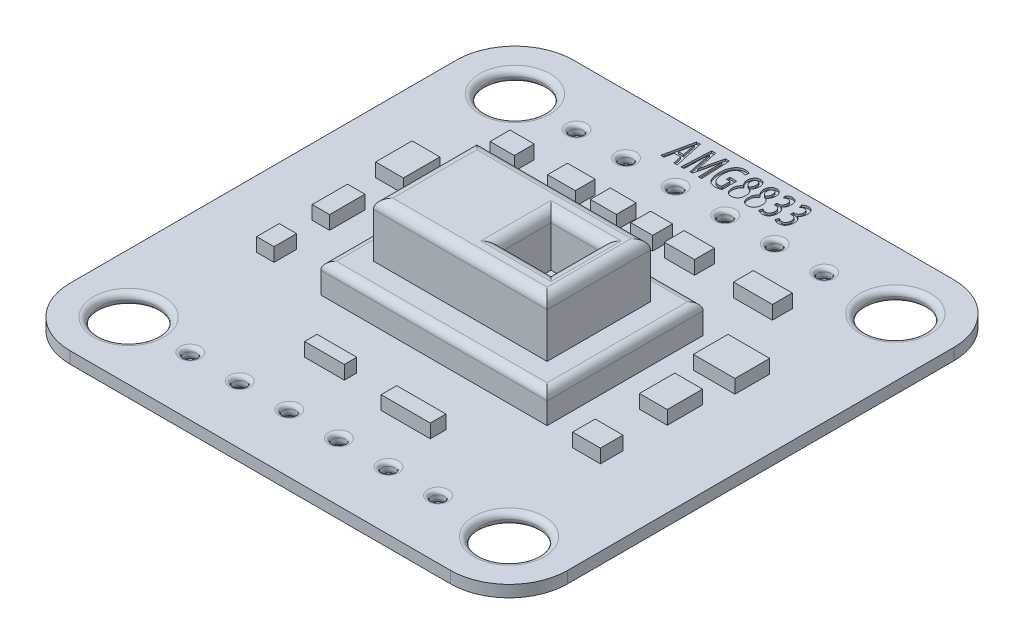
SolidWorks part; units mm, degrees
ref_plane "Alzado" through (0, 0, 0) normal (0, 0, 1) x (1, 0, 0)
ref_plane "Planta" through (0, 0, 0) normal (0, 1, 0) x (1, 0, 0)
ref_plane "Vista lateral" through (0, 0, 0) normal (1, 0, 0) x (0, 0, -1)
sketch "Croquis1" plane through (0, 0, 0) normal (0, 1, 0) x (1, 0, 0)
  line L1 (-12.75, 12.9) -> (12.75, 12.9)
  line L2 (-12.75, 12.9) -> (-12.75, -12.9)
  line L3 (-12.75, -12.9) -> (12.75, -12.9)
  line L4 (12.75, 12.9) -> (12.75, -12.9)
  line L5 (-12.75, 12.9) -> (12.75, -12.9) construction
  line L6 (-12.75, -12.9) -> (12.75, 12.9) construction
  point P0 (0, 0)
  dimension "D1" = 25.5
  dimension "D2" = 25.8
extrude "Saliente-Extruir1" add sketch "Croquis1" along normal blind 0.6
fillet "Redondeo1" radius 3 4 edges at (12.75, 0.3, 12.9) (-12.75, 0.3, 12.9) (12.75, 0.3, -12.9) (-12.75, 0.3, -12.9)
sketch "Croquis2" plane through (0, 0, 0) normal (0, -1, 0) x (1, 0, 0)
  circle A0 centre (9.75, -9.9) radius 1.5
  circle A1 centre (-9.75, -9.9) radius 1.5
  circle A2 centre (-9.75, 9.9) radius 1.5
  circle A3 centre (9.75, 9.9) radius 1.5
  dimension "D1" = 3
extrude "Cortar-Extruir1" cut sketch "Croquis2" against normal through all
fillet "Redondeo3" radius 0.3 8 edges at (-9.75, 0, 8.4) (-9.75, 0.6, 8.4) (9.75, 0, 8.4) (9.75, 0.6, 8.4) (-9.75, 0, -11.4) (-9.75, 0.6, -11.4) (9.75, 0, -11.4) (9.75, 0.6, -11.4)
sketch "Croquis3" plane through (0, 0.6, 0) normal (0, 1, 0) x (1, 0, 0)
  line L1 (-5.8, 4) -> (5.8, 4)
  line L2 (-5.8, 4) -> (-5.8, -4)
  line L3 (-5.8, -4) -> (5.8, -4)
  line L4 (5.8, 4) -> (5.8, -4)
  line L5 (-5.8, 4) -> (5.8, -4) construction
  line L6 (-5.8, -4) -> (5.8, 4) construction
  point P0 (0, 0)
  dimension "D1" = 11.6
  dimension "D2" = 8
extrude "Saliente-Extruir2" add sketch "Croquis3" along normal blind 1.5
sketch "Croquis4" plane through (0, 2.1, 0) normal (0, 1, 0) x (1, 0, 0)
  line L1 (-4.45, 2.65) -> (4.45, 2.65)
  line L2 (-4.45, 2.65) -> (-4.45, -2.65)
  line L3 (-4.45, -2.65) -> (4.45, -2.65)
  line L4 (4.45, 2.65) -> (4.45, -2.65)
  line L5 (-4.45, 2.65) -> (4.45, -2.65) construction
  line L6 (-4.45, -2.65) -> (4.45, 2.65) construction
  point P0 (0, 0)
  dimension "D1" = 5.3
  dimension "D2" = 8.9
extrude "Saliente-Extruir3" add sketch "Croquis4" along normal blind 2.8
fillet "Redondeo4" radius 0.4 4 edges at (0, 2.1, -4) (5.8, 2.1, 0) (0, 2.1, 4) (-5.8, 2.1, 0)
fillet "Redondeo5" radius 0.5 4 edges at (0, 4.9, 2.65) (-4.45, 4.9, 0) (0, 4.9, -2.65) (4.45, 4.9, 0)
sketch "Croquis5" plane through (0, 4.9, 0) normal (0, 1, 0) x (1, 0, 0)
  line L0 (0, 0) -> (2, 0) construction
  line L2 (0.7, 1.3) -> (3.3, 1.3)
  line L3 (0.7, 1.3) -> (0.7, -1.3)
  line L4 (0.7, -1.3) -> (3.3, -1.3)
  line L5 (3.3, 1.3) -> (3.3, -1.3)
  line L6 (0.7, 1.3) -> (3.3, -1.3) construction
  line L7 (0.7, -1.3) -> (3.3, 1.3) construction
  dimension "D1" = 2
  dimension "D2" = 2.6
  dimension "D3" = 2.6
extrude "Cortar-Extruir2" cut sketch "Croquis5" against normal blind 2.6
fillet "Redondeo6" radius 0.5 4 edges at (2, 4.9, -1.3) (2, 4.9, 1.3) (3.3, 4.9, 0) (0.7, 4.9, 0)
sketch "Croquis6" plane through (0, 0.6, 0) normal (0, 1, 0) x (1, 0, 0)
  line L0 (-6.9531, 6.9608) -> (7.3426, 6.9608) construction
  line L1 (7.3426, 6.9608) -> (7.3426, -7.1789) construction
  line L2 (7.3426, -7.1789) -> (-8.4928, -7.1789) construction
  line L3 (-8.4928, -7.1789) -> (-8.4928, 6.9608) construction
  line L4 (-8.4928, 6.9608) -> (-6.9531, 6.9608) construction
  line L6 (-7.5736, 7.4703) -> (-6.3325, 7.4703)
  line L7 (-7.5736, 7.4703) -> (-7.5736, 6.4512)
  line L8 (-7.5736, 6.4512) -> (-6.3325, 6.4512)
  line L9 (-6.3325, 7.4703) -> (-6.3325, 6.4512)
  line L10 (-7.5736, 7.4703) -> (-6.3325, 6.4512) construction
  line L11 (-7.5736, 6.4512) -> (-6.3325, 7.4703) construction
  line L12 (-4.6266, 7.4703) -> (-3.2087, 7.4703)
  line L13 (-4.6266, 7.4703) -> (-4.6266, 6.4512)
  line L14 (-4.6266, 6.4512) -> (-3.2087, 6.4512)
  line L15 (-3.2087, 7.4703) -> (-3.2087, 6.4512)
  line L16 (-4.6266, 7.4703) -> (-3.2087, 6.4512) construction
  line L17 (-4.6266, 6.4512) -> (-3.2087, 7.4703) construction
  line L18 (-2.4332, 7.4703) -> (-1.1039, 7.4703)
  line L19 (-2.4332, 7.4703) -> (-2.4332, 6.4512)
  line L20 (-2.4332, 6.4512) -> (-1.1039, 6.4512)
  line L21 (-1.1039, 7.4703) -> (-1.1039, 6.4512)
  line L22 (-2.4332, 7.4703) -> (-1.1039, 6.4512) construction
  line L23 (-2.4332, 6.4512) -> (-1.1039, 7.4703) construction
  line L24 (-0.3676, 7.4703) -> (0.7571, 7.4703)
  line L25 (-0.3676, 7.4703) -> (-0.3676, 6.4512)
  line L26 (-0.3676, 6.4512) -> (0.7571, 6.4512)
  line L27 (0.7571, 7.4703) -> (0.7571, 6.4512)
  line L28 (-0.3676, 7.4703) -> (0.7571, 6.4512) construction
  line L29 (-0.3676, 6.4512) -> (0.7571, 7.4703) construction
  line L30 (1.3553, 7.4703) -> (2.9061, 7.4703)
  line L31 (1.3553, 7.4703) -> (1.3553, 6.4512)
  line L32 (1.3553, 6.4512) -> (2.9061, 6.4512)
  line L33 (2.9061, 7.4703) -> (2.9061, 6.4512)
  line L34 (1.3553, 7.4703) -> (2.9061, 6.4512) construction
  line L35 (1.3553, 6.4512) -> (2.9061, 7.4703) construction
  line L36 (4.9001, 7.4703) -> (6.8941, 7.4703)
  line L37 (4.9001, 7.4703) -> (4.9001, 6.4512)
  line L38 (4.9001, 6.4512) -> (6.8941, 6.4512)
  line L39 (6.8941, 7.4703) -> (6.8941, 6.4512)
  line L40 (4.9001, 7.4703) -> (6.8941, 6.4512) construction
  line L41 (4.9001, 6.4512) -> (6.8941, 7.4703) construction
  line L42 (7.0834, 3.9891) -> (9.219, 3.9891)
  line L43 (7.0834, 3.9891) -> (7.0834, 2.2094)
  line L44 (7.0834, 2.2094) -> (9.219, 2.2094)
  line L45 (9.219, 3.9891) -> (9.219, 2.2094)
  line L46 (7.0834, 3.9891) -> (9.219, 2.2094) construction
  line L47 (7.0834, 2.2094) -> (9.219, 3.9891) construction
  line L48 (7.4393, 0.905) -> (8.8631, 0.905)
  line L49 (7.4393, 0.905) -> (7.4393, -0.905)
  line L50 (7.4393, -0.905) -> (8.8631, -0.905)
  line L51 (8.8631, 0.905) -> (8.8631, -0.905)
  line L52 (7.4393, 0.905) -> (8.8631, -0.905) construction
  line L53 (7.4393, -0.905) -> (8.8631, 0.905) construction
  line L54 (7.4393, -3.174) -> (8.8631, -3.174)
  line L55 (7.4393, -3.174) -> (7.4393, -4.3308)
  line L56 (7.4393, -4.3308) -> (8.8631, -4.3308)
  line L57 (8.8631, -3.174) -> (8.8631, -4.3308)
  line L58 (7.4393, -3.174) -> (8.8631, -4.3308) construction
  line L59 (7.4393, -4.3308) -> (8.8631, -3.174) construction
  line L60 (-3.4521, -6.543) -> (-1.4144, -6.543)
  line L61 (-3.4521, -6.543) -> (-3.4521, -7.1789)
  line L62 (-3.4521, -7.1789) -> (-1.4144, -7.1789)
  line L63 (-1.4144, -6.543) -> (-1.4144, -7.1789)
  line L64 (-3.4521, -6.543) -> (-1.4144, -7.1789) construction
  line L65 (-3.4521, -7.1789) -> (-1.4144, -6.543) construction
  line L66 (0.8708, -6.7792) -> (3.3907, -6.7792)
  line L67 (0.8708, -6.7792) -> (0.8708, -7.5786)
  line L68 (0.8708, -7.5786) -> (3.3907, -7.5786)
  line L69 (3.3907, -6.7792) -> (3.3907, -7.5786)
  line L70 (0.8708, -6.7792) -> (3.3907, -7.5786) construction
  line L71 (0.8708, -7.5786) -> (3.3907, -6.7792) construction
  line L72 (-8.177, 4.4785) -> (-9.6007, 4.4785)
  line L73 (-8.177, 4.4785) -> (-8.177, 2.6098)
  line L74 (-8.177, 2.6098) -> (-9.6007, 2.6098)
  line L75 (-9.6007, 4.4785) -> (-9.6007, 2.6098)
  line L76 (-8.177, 4.4785) -> (-9.6007, 2.6098) construction
  line L77 (-8.177, 2.6098) -> (-9.6007, 4.4785) construction
  line L78 (-8.444, 0.905) -> (-9.3338, 0.905)
  line L79 (-8.444, 0.905) -> (-8.444, -0.905)
  line L80 (-8.444, -0.905) -> (-9.3338, -0.905)
  line L81 (-9.3338, 0.905) -> (-9.3338, -0.905)
  line L82 (-8.444, 0.905) -> (-9.3338, -0.905) construction
  line L83 (-8.444, -0.905) -> (-9.3338, 0.905) construction
  line L84 (-8.444, -2.5956) -> (-9.3338, -2.5956)
  line L85 (-8.444, -2.5956) -> (-8.444, -3.7524)
  line L86 (-8.444, -3.7524) -> (-9.3338, -3.7524)
  line L87 (-9.3338, -2.5956) -> (-9.3338, -3.7524)
  line L88 (-8.444, -2.5956) -> (-9.3338, -3.7524) construction
  line L89 (-8.444, -3.7524) -> (-9.3338, -2.5956) construction
  point P9 (-3.9176, 6.9608)
  point P14 (-1.7686, 6.9608)
  point P19 (0.1948, 6.9608)
  point P24 (2.1307, 6.9608)
  point P29 (5.8971, 6.9608)
  point P34 (8.1512, 3.0992)
  point P39 (8.1512, 0)
  point P44 (8.1512, -3.7524)
  point P49 (-2.4332, -6.861)
  point P54 (2.1307, -7.1789)
  point P59 (-8.8889, 3.5441)
  point P64 (-8.8889, 0)
  point P69 (-8.8889, -3.174)
extrude "Saliente-Extruir4" add sketch "Croquis6" along normal blind 0.7
sketch "Croquis7" plane through (0, 0.6, 0) normal (0, 1, 0) x (1, 0, 0)
  line L0 (-19.5537, 0) -> (19.4797, 0) construction
  line L1 (-7.95, -9.9) -> (7.95, -9.9) construction
  line L2 (-6.5941, 9.9) -> (-4.0541, 9.9) construction
  line L3 (-4.0541, 9.9) -> (-1.5141, 9.9) construction
  line L4 (-1.5141, 9.9) -> (1.0259, 9.9) construction
  line L5 (1.0259, 9.9) -> (3.5659, 9.9) construction
  line L6 (3.5659, 9.9) -> (6.1059, 9.9) construction
  circle A2 centre (-9.75, -9.9) radius 1.8 construction
  circle A3 centre (9.75, -9.9) radius 1.8 construction
  circle A4 centre (-6.5941, 9.9) radius 0.325
  circle A5 centre (-4.0541, 9.9) radius 0.325
  circle A6 centre (-1.5141, 9.9) radius 0.325
  circle A7 centre (1.0259, 9.9) radius 0.325
  circle A8 centre (3.5659, 9.9) radius 0.325
  circle A9 centre (6.1059, 9.9) radius 0.325
  circle A10 centre (6.1059, -9.9) radius 0.325
  circle A11 centre (3.5659, -9.9) radius 0.325
  circle A12 centre (1.0259, -9.9) radius 0.325
  circle A13 centre (-1.5141, -9.9) radius 0.325
  circle A14 centre (-4.0541, -9.9) radius 0.325
  circle A15 centre (-6.5941, -9.9) radius 0.325
  dimension "D1" = 0.65
  dimension "D2" = 2.54
extrude "Cortar-Extruir3" cut sketch "Croquis7" against normal through all
fillet "Redondeo7" radius 0.2 9 edges at (3.5659, 0.6, -9.575) (3.5659, 0, -9.575) (-1.5141, 0.6, -9.575) (-1.5141, 0, -9.575) (-4.0541, 0.6, -9.575) (-4.0541, 0, -9.575) (-6.5941, 0.6, -9.575) (-6.5941, 0, -9.575) (1.0259, 0, -9.575)
fillet "Redondeo8" radius 0.2 15 edges at (6.1059, 0.6, 9.575) (6.1059, 0, 9.575) (3.5659, 0.6, 9.575) (3.5659, 0, 9.575) (1.0259, 0.6, 9.575) (1.0259, 0, 9.575) (-1.5141, 0.6, 9.575) (-1.5141, 0, 9.575) (-4.0541, 0.6, 9.575) (-4.0541, 0, 9.575) (-6.5941, 0.6, 9.575) (-6.5941, 0, 9.575) (1.0259, 0.6, -9.575) (6.1059, 0.6, -9.575) (6.1059, 0, -9.575)
sketch "Croquis8" plane through (0, 0.6, 0) normal (0, 1, 0) x (1, 0, 0)
  text T0 "<b>AMG8833</b>" font "@Adobe Heiti Std R" height 1.5
extrude "Cortar-Extruir4" cut sketch "Croquis8" against normal blind 0.1
